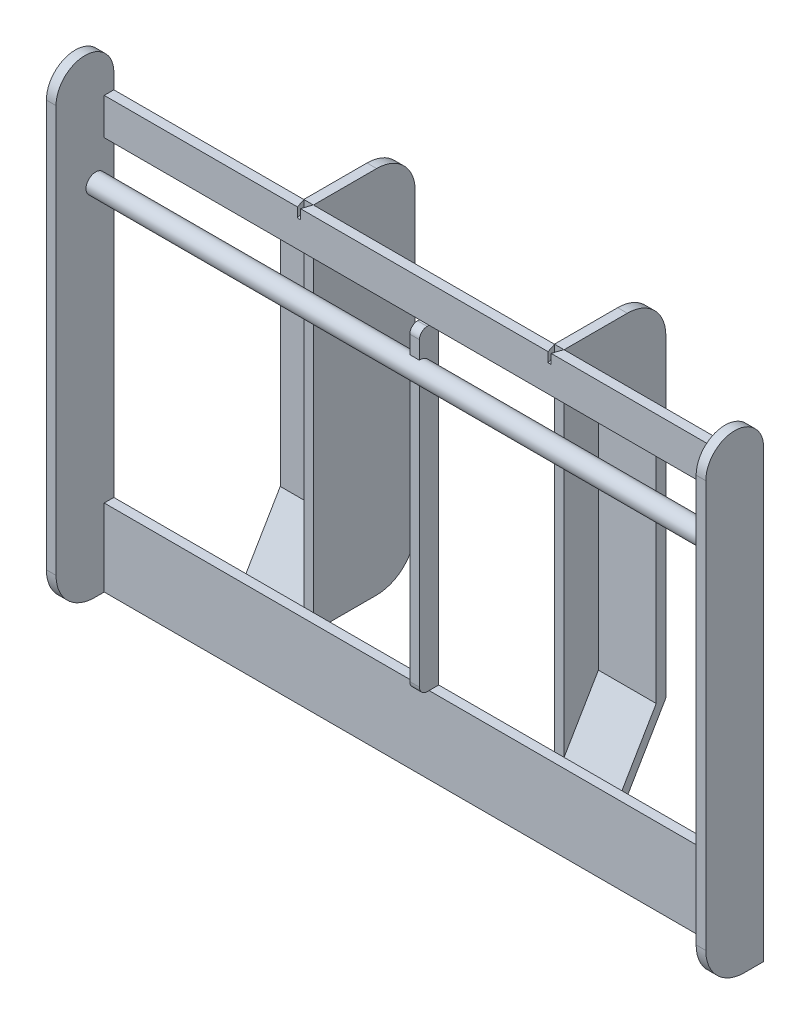
SolidWorks part; units mm, degrees
ref_plane "Front Plane" through (0, 0, 0) normal (0, 0, 1) x (1, 0, 0)
ref_plane "Top Plane" through (0, 0, 0) normal (0, 1, 0) x (1, 0, 0)
ref_plane "Right Plane" through (0, 0, 0) normal (1, 0, 0) x (0, 0, -1)
sketch "Sketch1" plane through (0, 0, 0) normal (0, 1, 0) x (1, 0, 0)
  line L5 (312.5, 132) -> (337.5, 132)
  line L6 (312.5, 132) -> (312.5, -132)
  line L7 (312.5, -132) -> (337.5, -132)
  line L8 (337.5, 132) -> (337.5, -132)
  point P10 (312.5, 0)
  dimension "D4" = 25
  dimension "D5" = 312.5
  dimension "D6" = 264
extrude "Boss-Extrude1" add sketch "Sketch1" against normal blind 958
sketch "Sketch2" plane through (337.5, 0, 0) normal (1, 0, 0) x (0, 0, -1)
  line L0 (132, -958) -> (132, 0) construction
  line L2 (-43, -139.55) -> (-43, -763.99)
  line L4 (-18, -139.55) -> (-18, -763.99)
  line L6 (-18, -139.55) -> (-132, 0)
  line L8 (-132, 0) -> (-132, -30.6031)
  line L9 (-132, -958) -> (-132, 0) construction
  line L10 (-132, -30.6031) -> (-43, -139.55)
  line L11 (-18, -763.99) -> (-132, -958)
  line L12 (-132, -958) -> (-132, -915.4539)
  line L13 (-132, -915.4539) -> (-43, -763.99)
  line L14 (-132, 0) -> (132, 0) construction
  dimension "D1" = 624.44
  dimension "D2" = 150
  dimension "D3" = 25
  dimension "D4" = 624.44
  dimension "D5" = 139.55
extrude "Boss-Extrude2" add sketch "Sketch2" along normal blind 150
mirror "Mirror2" about plane through (0, 0, 0) normal (1, 0, 0) of bodies 103
sketch "Sketch3" plane through (0, 0, 132) normal (0, 0, 1) x (1, 0, 0)
  line L1 (-830, 0) -> (830, 0)
  line L2 (-830, 0) -> (-830, -95)
  line L3 (-830, -95) -> (830, -95)
  line L4 (830, 0) -> (830, -95)
  line L6 (-487.5, -915.4539) -> (-337.5, -915.4539) construction
  line L7 (-830, -915.4539) -> (830, -915.4539)
  line L8 (-830, -915.4539) -> (-830, -1115.4539)
  line L9 (-830, -1115.4539) -> (830, -1115.4539)
  line L10 (830, -915.4539) -> (830, -1115.4539)
  dimension "D1" = 95
  dimension "D2" = 1660
  dimension "D3" = 200
  dimension "D4" = 1660
extrude "Boss-Extrude3" add sketch "Sketch3" along normal blind 25
sketch "Sketch4" plane through (830, 0, 0) normal (1, 0, 0) x (0, 0, -1)
  line L1 (-132, -1115.4539) -> (-282, -1115.4539)
  line L2 (-132, -1115.4539) -> (-132, 114.5461)
  line L3 (-132, 114.5461) -> (-282, 114.5461)
  line L4 (-282, -1115.4539) -> (-282, 114.5461)
  dimension "D1" = 150
  dimension "D2" = 1230
extrude "Boss-Extrude4" add sketch "Sketch4" along normal blind 25
mirror "Mirror3" about plane through (0, 0, 0) normal (1, 0, 0) of "Boss-Extrude4"
sketch "Sketch5" plane through (0, 0, 0) normal (1, 0, 0) x (0, 0, -1)
  line L0 (227.7, 0) -> (-227.7, 0) construction
  circle A0 centre (-179.2, -185.96) radius 25
  dimension "D3" = 50
  dimension "D1" = 47.2
  dimension "D2" = 185.96
extrude "Boss-Extrude5" add sketch "Sketch5" along normal up to next and the other way up to next
sketch "Sketch6" plane through (0, -95, 0) normal (0, -1, 0) x (1, 0, 0)
  line L0 (-830, 157) -> (830, 157) construction
  line L1 (12.5, 182) -> (-12.5, 182)
  line L2 (12.5, 182) -> (12.5, 132)
  line L3 (12.5, 132) -> (-12.5, 132)
  line L4 (-12.5, 182) -> (-12.5, 132)
  line L5 (12.5, 182) -> (-12.5, 132) construction
  line L6 (12.5, 132) -> (-12.5, 182) construction
  line L7 (-855, 132) -> (855, 132) construction
  point P0 (0, 157)
  dimension "D1" = 25
extrude "Boss-Extrude6" add sketch "Sketch6" along normal up to surface (820.4539 mm away) up to face at (0, -915.4539, 137)
fillet "Fillet1" 2 edges at (842.5, 114.5461, 282) (842.5, 114.5461, 132) type full round first side face at (842.5, -500.4539, 282) second side face at (0, -413.8623, 132) middle face at (842.5, 114.5461, 207)
fillet "Fillet2" 2 edges at (-842.5, 114.5461, 132) (-842.5, 114.5461, 282) type full round first side face at (0, -417.8097, 132) second side face at (-842.5, -500.4539, 282) middle face at (-842.5, 114.5461, 207)
fillet "Fillet3" radius 100 1 edges at (-325, 0, -132) type face fillet first side face at (0, 0, 60.1429) second side face at (-325, -479, -132)
fillet "Fillet4" radius 100 1 edges at (325, 0, -132) type face fillet first side face at (0, 0, 74.4286) second side face at (325, -479, -132)
fillet "Fillet5" radius 100 1 edges at (325, -958, -132) type face fillet first side face at (325, -529, -132) second side face at (325, -958, 0)
fillet "Fillet6" radius 100 1 edges at (-325, -958, -132) type face fillet first side face at (-325, -529, -132) second side face at (-325, -958, 0)
fillet "Fillet7" radius 20 1 edges at (0, -95, 182) type face fillet first side face at (0, -95, 169.5) second side face at (0, -128.0586, 182)
fillet "Fillet8" radius 20 1 edges at (0, -915.4539, 182) type face fillet first side face at (0, -563.1283, 182) second side face at (0, -915.4539, 169.5)
fillet "Fillet9" radius 100 1 edges at (842.5, -1115.4539, 282) type face fillet first side face at (842.5, -537.9539, 282) second side face at (0, -1115.4539, 213.25)
fillet "Fillet10" radius 100 1 edges at (-842.5, -1115.4539, 282) type face fillet first side face at (-842.5, -537.9539, 282) second side face at (0, -1115.4539, 188.25)
sketch "Sketch7" plane through (0, 0, 0) normal (0, 1, 0) x (1, 0, 0)
  line L4 (337, -132) -> (313, -132)
  line L5 (325, -132) -> (325, -157) construction
  line L6 (830, -157) -> (-830, -157) construction
  line L9 (313, -132) -> (321, -157)
  line L10 (321, -157) -> (329, -157)
  line L11 (329, -157) -> (337, -132)
  dimension "D1" = 4
  dimension "D2" = 4
  dimension "D3" = 12
extrude "Cut-Extrude5" cut sketch "Sketch7" against normal blind 25
mirror "Mirror4" about plane through (0, 0, 0) normal (1, 0, 0) of "Cut-Extrude5"
